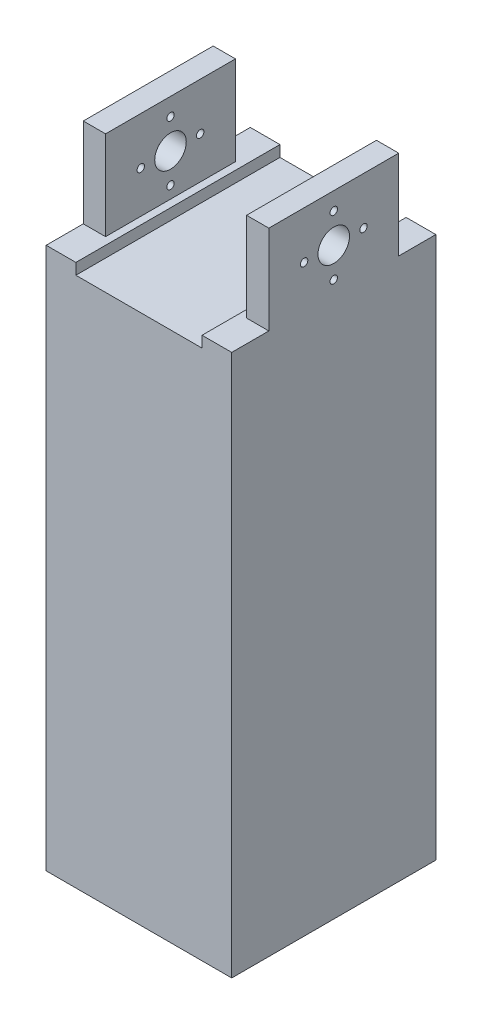
SolidWorks part; units mm, degrees
ref_plane "Front Plane" through (0, 0, 0) normal (0, 0, 1) x (1, 0, 0)
ref_plane "Top Plane" through (0, 0, 0) normal (0, 1, 0) x (1, 0, 0)
ref_plane "Right Plane" through (0, 0, 0) normal (1, 0, 0) x (0, 0, -1)
sketch "Sketch1" plane through (0, 0, 0) normal (0, 0, 1) x (1, 0, 0)
  line L1 (-25, 0) -> (25, 0)
  line L2 (-25, 0) -> (-25, -170)
  line L3 (-25, -170) -> (25, -170)
  line L4 (25, 0) -> (25, -170)
  dimension "D1" = 170
  dimension "D2" = 50
extrude "Boss-Extrude1" add sketch "Sketch1" against normal blind 55
sketch "Sketch2" plane through (0, 0, 0) normal (0, 0, 1) x (1, 0, 0)
  line L0 (25, 0) -> (-25, 0) construction
  line L1 (-17, 0) -> (17, 0)
  line L2 (-17, 0) -> (-17, -27)
  line L3 (-17, -27) -> (17, -27)
  line L4 (17, 0) -> (17, -27)
  line L5 (-25, 0) -> (-25, -170) construction
  dimension "D1" = 8
  dimension "D2" = 34
  dimension "D3" = 27
extrude "Cut-Extrude1" cut sketch "Sketch2" against normal through all
sketch "Sketch3" plane through (25, 0, 0) normal (1, 0, 0) x (0, 0, -1)
  line L0 (0, -170) -> (0, 0) construction
  line L1 (55, -27) -> (0, -27)
  line L2 (55, -27) -> (55, -24)
  line L3 (55, -24) -> (0, -24)
  line L4 (0, -27) -> (0, -24)
  line L5 (55, -170) -> (55, 0) construction
  line L7 (0, 0) -> (10, 0)
  line L8 (0, 0) -> (0, -24)
  line L9 (0, -24) -> (10, -24)
  line L10 (10, 0) -> (10, -24)
  line L11 (55, 0) -> (45, 0)
  line L12 (55, 0) -> (55, -24)
  line L13 (55, -24) -> (45, -24)
  line L14 (45, 0) -> (45, -24)
  circle A0 centre (27.5, -12.75) radius 10.25
  circle A1 centre (27.5, -12.75) radius 4.25
  circle A2 centre (27.5, -12.75) radius 8
  circle A3 centre (27.5, -4.75) radius 1
  circle A4 centre (35.5, -12.75) radius 1
  circle A5 centre (27.5, -20.75) radius 1
  circle A6 centre (19.5, -12.75) radius 1
  point P32 (27.5, -12.75)
  line M7 (0, 0) -> (0, -170)
  line M9 (55, -170) -> (55, 0)
  line M10 (55, 0) -> (0, 0)
  dimension "D2" = 11.25
  dimension "D3" = 27.5
  dimension "D4" = 20.5
  dimension "D7" = 8.5
  dimension "D8" = 16
  dimension "D9" = 4
  dimension "D1" = 3
  dimension "D5" = 10
  dimension "D6" = 10
extrude "Cut-Extrude2" cut sketch "Sketch3" against normal through all contours L14 L3 M10 M9 | L10 L3 M10 M7 | A2 A6 | A2 A6 | A1 | A2 A5 | A2 A5 | A2 A4 | A2 A4 | A2 A3 | A2 A3 region at (25, -12, -50) region at (25, -12, -5) region at (25, -12.75, -27.5) region at (25, -12.75, -35.0645) region at (25, -12.75, -35.913) region at (25, -5.1855, -27.5) region at (25, -4.337, -27.5) region at (25, -21.163, -27.5) region at (25, -20.3145, -27.5) region at (25, -12.75, -19.9355) region at (25, -12.75, -19.087)
sketch "Sketch4" plane through (0, 0, -10) normal (0, 0, 1) x (1, 0, 0)
  line L0 (-25, -24) -> (-17, -24) construction
  line L1 (-17, 0) -> (-19, 0)
  line L2 (-17, 0) -> (-17, -24)
  line L3 (-17, -24) -> (-19, -24)
  line L4 (-19, 0) -> (-19, -24)
  line L5 (0, 0) -> (0, -13.53) construction
  line L6 (19, 0) -> (19, -24)
  line L7 (17, -24) -> (19, -24)
  line L8 (17, 0) -> (17, -24)
  line L9 (17, 0) -> (19, 0)
  dimension "D1" = 2
extrude "Cut-Extrude3" cut sketch "Sketch4" against normal through all
